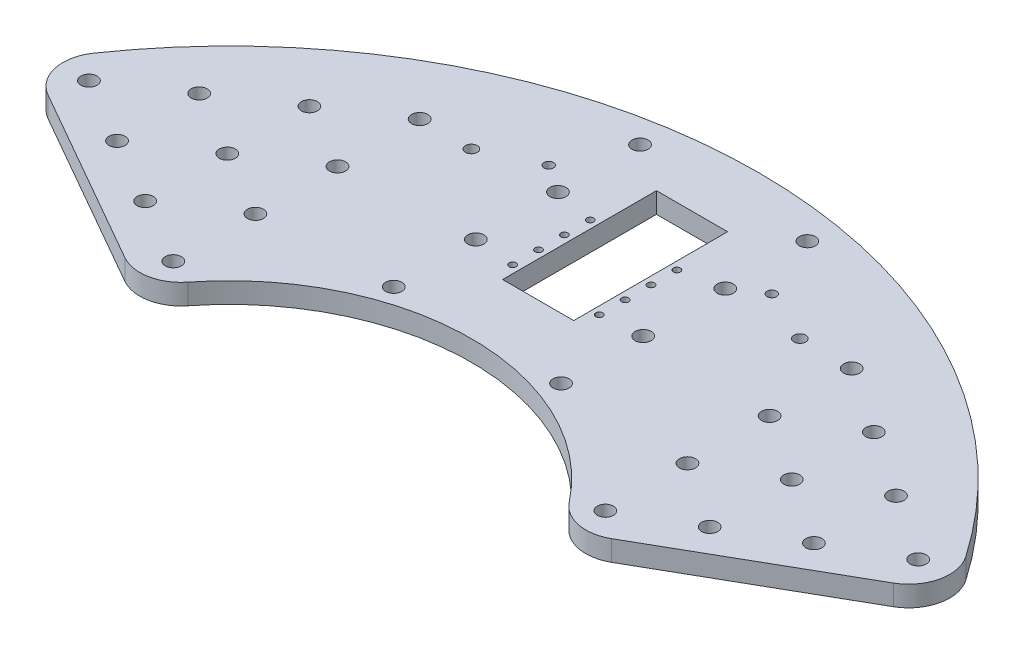
SolidWorks part; units mm, degrees
material "Oak"
ref_plane "Front Plane" through (0, 0, 0) normal (0, 0, 1) x (1, 0, 0)
ref_plane "Top Plane" through (0, 0, 0) normal (0, 1, 0) x (1, 0, 0)
ref_plane "Right Plane" through (0, 0, 0) normal (1, 0, 0) x (0, 0, -1)
sketch "Sketch1" plane through (0, 0, 0) normal (0, 1, 0) x (1, 0, 0)
  line L0 (0, 0) -> (0, 163.83) construction
  line L1 (0, 0) -> (0, 106.172) construction
  line L2 (-50.8, 106.172) -> (50.8, 106.172) construction
  line L3 (0, 163.83) -> (0, 74.93) construction
  line L4 (65.0581, 37.1746) -> (142.2457, 81.28)
  line L5 (-65.0581, 37.1746) -> (-142.2457, 81.28)
  arc A0 (-142.2457, 81.28) -> (142.2457, 81.28) centre (0, 0) cw
  arc A1 (-65.0581, 37.1746) -> (65.0581, 37.1746) centre (0, 0) cw
  dimension "D1" = 163.83
  dimension "D4" = 74.93
  dimension "D2" = 106.172
  dimension "D3" = 50.8
  dimension "D5" = 88.9
  dimension "D6" = 24.892
extrude "Boss-Extrude1" add sketch "Sketch1" along normal blind 6.35
ref_axis "Axis1" through (0, 6.35, -52.1043) along (0, 0, -1)
ref_point "Point1"
hole_wizard "#6 Clearance Hole1" positions "3DSketch1" profile "Sketch2" hole size "#6" standard "Ansi Inch"
sketch3d "3DSketch1"
  line L0 (0, 6.35, -74.93) -> (0, 6.35, -125.73) construction
  line L1 (0, 6.35, -52.1043) -> (0, 6.35, -180.2482) construction
  line L3 (50.8, 6.35, -125.73) -> (-50.8, 6.35, -125.73) construction
  arc A0 (-65.0581, 6.35, -37.1746) -> (65.0581, 6.35, -37.1746) centre (0, 6.35, 0) ccw construction
  point P12 (0, -68.58, 0)
  point P28 (-50.8, 6.35, -125.73)
  point P30 (50.8, 6.35, -125.73)
  dimension "D1" = 50.8
  dimension "D2" = 101.6
  dimension "D3" = 50.8
sketch "Sketch2" plane through (-50.8, 6.35, -125.73) normal (1, 0, 0) x (0, 0, 1)
  line L0 (0, 0) -> (0, 26.4989)
  line L1 (0, 26.4989) -> (1.8288, 25.4)
  line L2 (1.8288, 25.4) -> (1.8288, 0)
  line L5 (1.8288, 0) -> (0, 0)
  line L10 (0, 26.4989) -> (-1.8288, 25.4) construction
  line L11 (0, -6.35) -> (0, 107.95) construction
  dimension "Hole Dia." = 3.6576
  dimension "Hole Depth" = 25.4
  dimension "Drill Angle" = 118
fillet "Fillet1" radius 12.7 4 edges at (65.0581, 3.175, -37.1746) (-142.2457, 3.175, -81.28) (-65.0581, 3.175, -37.1746) (142.2457, 3.175, -81.28)
hole_wizard "#4 Clearance Hole1" positions "Sketch4" profile "Sketch3" hole size "#4" standard "Ansi Inch"
sketch "Sketch4" plane through (0, 6.35, 0) normal (0, 1, 0) x (-1, 0, 0)
  line L0 (0, -52.1043) -> (0, -180.2482) construction
  line L1 (0, -163.83) -> (0, -80.1707) construction
  arc A0 (-134.9123, -92.9459) -> (134.9123, -92.9459) centre (0, 0) ccw construction
  point P0 (-34.5, -133.35)
  point P4 (0, -163.83)
  point P14 (34.5, -133.35)
  dimension "D1" = 34.5
  dimension "D2" = 30.48
sketch "Sketch3" plane through (34.5, 6.35, -133.35) normal (1, 0, 0) x (0, 0, 1)
  line L0 (0, 0) -> (0, 26.2852)
  line L1 (0, 26.2852) -> (1.4732, 25.4)
  line L2 (1.4732, 25.4) -> (1.4732, 0)
  line L5 (1.4732, 0) -> (0, 0)
  line L10 (0, 26.2852) -> (-1.4732, 25.4) construction
  line L11 (0, -6.35) -> (0, 107.95) construction
  dimension "Hole Dia." = 2.9464
  dimension "Hole Depth" = 25.4
  dimension "Drill Angle" = 118
hole_wizard "#10 Clearance Hole1" positions "Sketch6" profile "Sketch5" hole size "#10" standard "Ansi Inch"
sketch "Sketch6" plane through (0, 6.35, 0) normal (0, 1, 0) x (-1, 0, 0)
  line L0 (128.2551, -84.874) -> (130.7547, -74.714) construction
  line L2 (128.2551, -84.874) -> (134.9123, -92.9459) construction
  line L4 (75.2816, -43.0163) -> (69.8344, -34.44) construction
  line L5 (69.8344, -34.44) -> (66.5461, -34.44) construction
  arc A0 (-134.9123, -92.9459) -> (134.9123, -92.9459) centre (0, 0) ccw construction
  arc A1 (134.9123, -92.9459) -> (130.7547, -74.714) centre (124.454, -85.7408) ccw construction
  arc A2 (-58.9836, -46.2108) -> (58.9836, -46.2108) centre (0, 0) ccw construction
  point P0 (128.2551, -84.874)
  dimension "D1" = 10.16
  dimension "D2" = 10.16
sketch "Sketch5" plane through (-128.2551, 6.35, -84.874) normal (1, 0, 0) x (0, 0, 1)
  line L0 (0, 0) -> (0, 26.8957)
  line L1 (0, 26.8957) -> (2.4892, 25.4)
  line L2 (2.4892, 25.4) -> (2.4892, 0)
  line L5 (2.4892, 0) -> (0, 0)
  line L10 (0, 26.8957) -> (-2.4892, 25.4) construction
  line L11 (0, -6.35) -> (0, 107.95) construction
  dimension "Hole Dia." = 4.9784
  dimension "Hole Depth" = 25.4
  dimension "Drill Angle" = 118
ref_point "Point3"
sketch "Sketch7" plane through (0, 6.35, 0) normal (0, 1, 0) x (-1, 0, 0)
  line L0 (75.2816, -43.0163) -> (68.2586, -50.3582) construction
  line L1 (68.2586, -50.3582) -> (58.9836, -46.2108) construction
  dimension "D1" = 10.16
ref_axis "Axis4" through (-128.2551, 6.35, -84.874) along (0.8668, 0, 0.4987)
pattern_linear "LPattern4" count 6 spacing 25.4 along (0, 0, -1) count 7 spacing 23.622 along (0.8668, 0, 0.4987) skipping (0, 4), (0, 5), (0, 6), (1, 0), (1, 4), (1, 5), (1, 6), (2, 0), (2, 1), (2, 4), (2, 6), (3, 0), (3, 1), (3, 2), (3, 4), (3, 6), (4, 0), (4, 1), (4, 2), (4, 3), (4, 4), (4, 6), (5, 0), (5, 1), (5, 2), (5, 3), (5, 4), (5, 6) of "#10 Clearance Hole1"
ref_plane "Plane1" through (0, 0, 0) normal (1, 0, 0) x (0, 0, -1)
mirror "Mirror4" about plane through (0, 0, 0) normal (1, 0, 0) of "LPattern4"
sketch "Sketch8" plane through (0, 6.35, 0) normal (0, 1, 0) x (1, 0, 0)
  line L0 (0, 163.83) -> (0, 74.93) construction
  line L1 (0, -76.3978) -> (0, 76.3978) construction
  line L2 (-11, 143.18) -> (-11, 95.58)
  line L3 (-11, 143.18) -> (11, 143.18)
  line L4 (-11, 95.58) -> (11, 95.58)
  line L5 (11, 143.18) -> (11, 95.58)
  line L6 (-11, 143.18) -> (11, 95.58) construction
  line L7 (-11, 95.58) -> (11, 143.18) construction
  arc A0 (134.9123, 92.9459) -> (-134.9123, 92.9459) centre (0, 0) ccw construction
  arc A1 (58.9836, 46.2108) -> (-58.9836, 46.2108) centre (0, 0) ccw construction
  point P0 (0, 163.83)
  point P1 (0, 74.93)
  point P12 (-13.4, 125.08)
  point P13 (0, 119.38)
  point P14 (-13.4, 117.08)
  point P15 (-13.4, 109.08)
  point P20 (-13.4, 101.08)
  point P21 (13.4, 125.08)
  point P22 (13.4, 117.08)
  point P23 (13.4, 109.08)
  point P24 (13.4, 101.08)
  dimension "D1" = 88.9
  dimension "D2" = 47.6
  dimension "D3" = 22
  dimension "D4" = 2.4
  dimension "D5" = 18.1
  dimension "D6" = 8
  dimension "D7" = 8
  dimension "D8" = 8
extrude "Cut-Extrude1" cut sketch "Sketch8" against normal through all
hole_wizard "#4 Clearance Hole3" positions "Sketch16" profile "Sketch15" hole size "#4" standard "Ansi Inch" end condition through all
sketch "Sketch16" plane through (0, 6.35, 0) normal (0, 1, 0) x (-1, 0, 0)
  point P1 (13.4, -125.08)
  point P4 (13.4, -117.08)
  point P7 (13.4, -109.08)
  point P10 (13.4, -101.08)
  point P13 (-13.4, -101.08)
  point P16 (-13.4, -109.08)
  point P19 (-13.4, -117.08)
  point P22 (-13.4, -125.08)
sketch "Sketch15" plane through (-13.4, 6.35, -125.08) normal (1, 0, 0) x (0, 0, 1)
  line L0 (0, 0) -> (0, 6.35)
  line L1 (0, 6.35) -> (1.0795, 6.35)
  line L2 (1.0795, 6.35) -> (1.0795, 0)
  line L5 (1.0795, 0) -> (0, 0)
  line L11 (0, -6.35) -> (0, 107.95) construction
  dimension "Thru Hole Dia." = 2.159
  dimension "Thru Hole Depth" = 6.35
